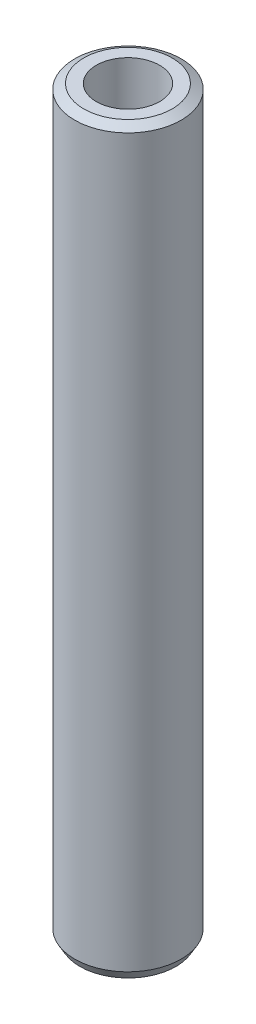
SolidWorks part; units mm, degrees
ref_plane "Front Plane" through (0, 0, 0) normal (0, 0, 1) x (1, 0, 0)
ref_plane "Top Plane" through (0, 0, 0) normal (0, 1, 0) x (1, 0, 0)
ref_plane "Right Plane" through (0, 0, 0) normal (1, 0, 0) x (0, 0, -1)
sketch "Sketch1" plane through (0, 0, 0) normal (0, 1, 0) x (1, 0, 0)
  circle A0 centre (0, 0) radius 30
  dimension "SHAFT_OD" = 60
extrude "Boss-Extrude1" add sketch "Sketch1" along normal blind 417.4838
sketch "Sketch2" plane through (0, 0, 0) normal (0, 1, 0) x (1, 0, 0)
  circle A0 centre (0, 0) radius 17.8105
  dimension "BORE_D" = 35.6211
extrude "Cut-Extrude1" cut sketch "Sketch2" along normal through all
chamfer "Chamfer1" distance 2.9442 angle 60 2 edges at (0, 417.4838, 30) (0, 0, 30) first distance on face at (0, 417.4838, 30) first distance on face at (0, 0, 17.8105)
